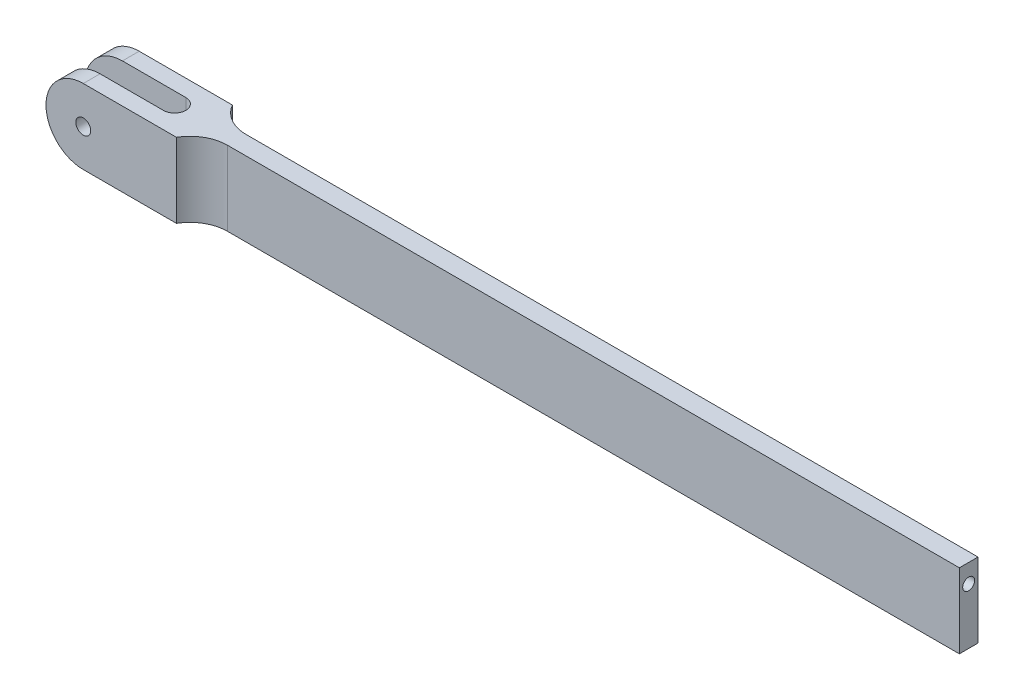
SolidWorks part; units mm, degrees
ref_plane "Front Plane" through (0, 0, 0) normal (0, 0, 1) x (1, 0, 0)
ref_plane "Top Plane" through (0, 0, 0) normal (0, 1, 0) x (1, 0, 0)
ref_plane "Right Plane" through (0, 0, 0) normal (1, 0, 0) x (0, 0, -1)
sketch "Sketch1" plane through (0, 0, 0) normal (0, 0, 1) x (1, 0, 0)
  line L0 (0, 0) -> (220, 0) construction
  line L1 (0, 10) -> (230, 10)
  line L2 (0, -10) -> (230, -10)
  line L3 (230, 10) -> (230, -10)
  arc A0 (0, 10) -> (0, -10) centre (0, 0) ccw
  circle A2 centre (0, 0) radius 2
  point P3 (60, 0)
  dimension "D3" = 4
  dimension "D1" = 220
  dimension "D2" = 20
  dimension "D4" = 10
  dimension "D5" = 20
extrude "Boss-Extrude1" add sketch "Sketch1" along normal blind 5
sketch "Sketch2" plane through (0, 0, 5) normal (0, 0, 1) x (1, 0, 0)
  line L0 (25, 10) -> (25, -10)
  line L2 (0, -10) -> (230, -10)
  line L3 (230, 10) -> (0, 10)
  line L4 (0, -10) -> (25, -10)
  line L5 (25, 10) -> (0, 10)
  line L8 (230, -10) -> (230, 10)
  line L9 (230, -10) -> (230, 10)
  circle A0 centre (0, 0) radius 2 construction
  circle A1 centre (0, 0) radius 2
  arc A2 (0, 10) -> (0, -10) centre (0, 0) ccw
  arc A4 (0, 10) -> (0, -10) centre (0, 0) ccw
  arc M6 (0, 10) -> (0, -10) centre (0, 0) ccw
  line M7 (0, -10) -> (230, -10)
  line M9 (230, 10) -> (0, 10)
  circle M10 centre (0, 0) radius 2
  dimension "D2" = 25
  dimension "D1" = 0
extrude "Boss-Extrude2" add sketch "Sketch2" along normal blind 5 and the other way blind 10 contours L0 M9 M6 M7 M10 region at (8.6629, 0, 5)
sketch "Sketch4" plane through (0, 10, 0) normal (0, 1, 0) x (1, 0, 0)
  line L0 (0, -10) -> (0, 5) construction
  line L1 (-20, 0.5) -> (20, 0.5)
  line L2 (-20, 0.5) -> (-20, -5.5)
  line L3 (-20, -5.5) -> (20, -5.5)
  line L4 (20, 0.5) -> (20, -5.5)
  line L5 (-20, 0.5) -> (20, -5.5) construction
  line L6 (-20, -5.5) -> (20, 0.5) construction
  point P0 (0, -2.5)
  dimension "D1" = 6
  dimension "D2" = 40
extrude "Cut-Extrude1" cut sketch "Sketch4" against normal through all
fillet "Fillet1" radius 10 2 edges at (25, 0, 5) (25, 0, 0)
fillet "Fillet2" radius 3 2 edges at (20, 0, -0.5) (20, 0, 5.5)
sketch "Sketch5" plane through (230, 0, 0) normal (1, 0, 0) x (0, 0, -1)
  line L0 (-2.5, 10) -> (-2.5, -10) construction
  line L1 (-5, 10) -> (0, 10) construction
  line L2 (-5, -10) -> (0, -10) construction
  circle A0 centre (-2.5, 5) radius 1.6
  point P12 (8.6809, -0.0554)
  dimension "D2" = 3.2
  dimension "D1" = 5
extrude "Cut-Extrude2" cut sketch "Sketch5" against normal blind 20
